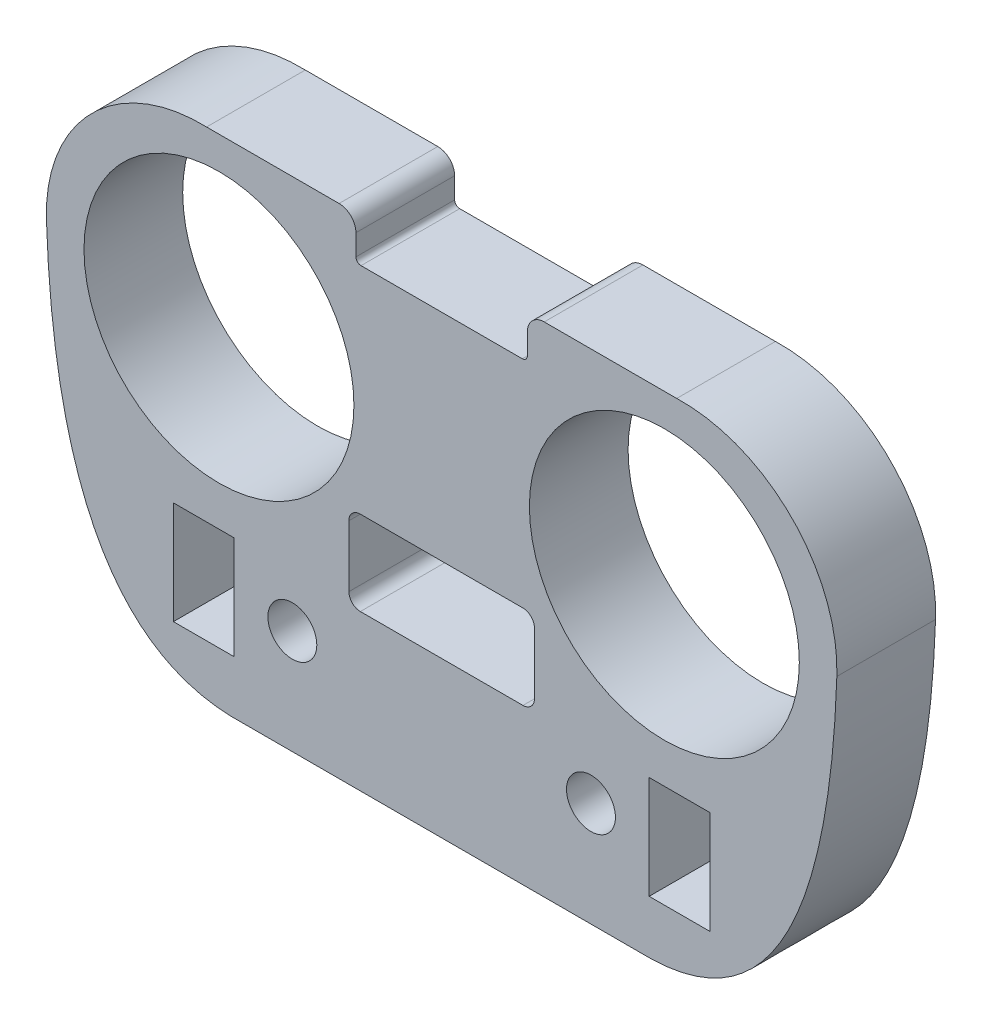
SolidWorks part; units mm, degrees
material "Acrylic (Medium-high impact)"
ref_plane "Front Plane" through (0, 0, 0) normal (0, 0, 1) x (1, 0, 0)
ref_plane "Top Plane" through (0, 0, 0) normal (0, 1, 0) x (1, 0, 0)
ref_plane "Right Plane" through (0, 0, 0) normal (1, 0, 0) x (0, 0, -1)
sketch "Model" plane through (0, 0, 0) normal (0, 0, 1) x (1, 0, 0)
  line L0 (549.8561, 574.3347) -> (554.6761, 574.3347)
  line L1 (554.6761, 576.8347) -> (549.1761, 576.8347) construction
  line L2 (554.6761, 576.8347) -> (560.1761, 576.8347) construction
  line L3 (554.6761, -405.4445) -> (554.6761, 49594.5555) construction
  line L4 (540.7427, 594.6497) -> (549.5961, 594.6497)
  line L5 (542.1922, 565.1247) -> (567.16, 565.1247)
  line L6 (549.8561, 579.3347) -> (554.6761, 579.3347)
  line L7 (566.9761, 574.3747) -> (566.9761, 568.2747)
  line L8 (570.5761, 574.3747) -> (566.9761, 574.3747)
  line L9 (570.5761, 568.2747) -> (570.5761, 574.3747)
  line L10 (566.9761, 568.2747) -> (570.5761, 568.2747)
  line L11 (560.1761, 578.6547) -> (560.1761, 575.0147)
  line L12 (559.4961, 579.3347) -> (554.6761, 579.3347)
  line L13 (559.4961, 574.3347) -> (554.6761, 574.3347)
  line L14 (538.7761, 571.3247) -> (570.5761, 571.3247) construction
  line L15 (541.4761, 584.7347) -> (567.8761, 584.7347) construction
  line L16 (549.5961, 592.1097) -> (559.7561, 592.1097)
  line L17 (549.5961, 592.1097) -> (549.5961, 594.6497)
  line L18 (559.7561, 592.1097) -> (559.7561, 594.6497)
  line L19 (559.7561, 594.6497) -> (568.6095, 594.6497)
  line L21 (549.1761, 578.6547) -> (549.1761, 575.0147)
  line L32 (542.3761, 568.2747) -> (538.7761, 568.2747)
  line L33 (538.7761, 568.2747) -> (538.7761, 574.3747)
  line L34 (538.7761, 574.3747) -> (542.3761, 574.3747)
  line L35 (542.3761, 574.3747) -> (542.3761, 568.2747)
  circle A0 centre (545.8261, 571.3247) radius 1.45
  arc A1 (578.1008, 585.1247) -> (568.6095, 594.6497) centre (568.8929, 585.4407) ccw
  circle A2 centre (541.4761, 584.7347) radius 8
  arc A3 (549.1761, 575.0147) -> (549.8561, 574.3347) centre (549.8561, 575.0147) ccw
  arc A4 (549.1761, 578.6547) -> (549.8561, 579.3347) centre (549.8561, 578.6547) cw
  arc A5 (560.1761, 578.6547) -> (559.4961, 579.3347) centre (559.4961, 578.6547) ccw
  arc A6 (560.1761, 575.0147) -> (559.4961, 574.3347) centre (559.4961, 575.0147) cw
  arc A7 (531.2514, 585.1247) -> (540.7427, 594.6497) centre (540.4593, 585.4407) cw
  circle A8 centre (567.8761, 584.7347) radius 8
  circle A9 centre (563.5261, 571.3247) radius 1.45
  spline S0 degree 2 poles (578.1008, 585.1247) (577.4253, 565.4445) (567.16, 565.1247) knots 0 0 0 1 1 1
  spline S48 degree 2 poles (531.2514, 585.1247) (531.9269, 565.4445) (542.1922, 565.1247) knots 0 0 0 1 1 1
  point P0 (554.6761, 571.3247)
  point P19 (549.4761, 584.7347)
  point P32 (559.8761, 584.7347)
  point P33 (554.6761, 584.7347)
  point P34 (554.6761, 565.1247)
  point P36 (554.6761, 576.8347)
  point P40 (554.6761, 592.1097)
  dimension "D11" = 2.9
  dimension "D12" = 16
  dimension "D14" = 0.68
  dimension "D16" = 10.16
  dimension "D1" = 3.45
  dimension "D2" = 8.85
  dimension "D3" = 20
  dimension "D4" = 6.1
  dimension "D5" = 11
  dimension "D6" = 5
  dimension "D7" = 3.6
  dimension "D8" = 29.525
  dimension "D9" = 6.2
  dimension "D10" = 0.04
  dimension "D13" = 10.4
  dimension "D15" = 7.9
  dimension "D17" = 2.54
  dimension "D18" = 5.51
extrude "Boss-Extrude1" add sketch "Model" along normal blind 5.85 contours A7 S48 L5 S0 A1 L4 A9 L11 A6 L13 L0 A3 L21 A4 L6 L12 A5 A2 A0 L10 L7 L8 L9 L34 L35 L32 L33 A8 region at (545.1694, 594.0958, 0)
fillet "Fillet1" radius 0.3 2 edges at (559.7561, 592.1097, 2.925) (549.5961, 592.1097, 2.925)
fillet "Fillet2" radius 1 2 edges at (559.7561, 594.6497, 2.925) (549.5961, 594.6497, 2.925)
